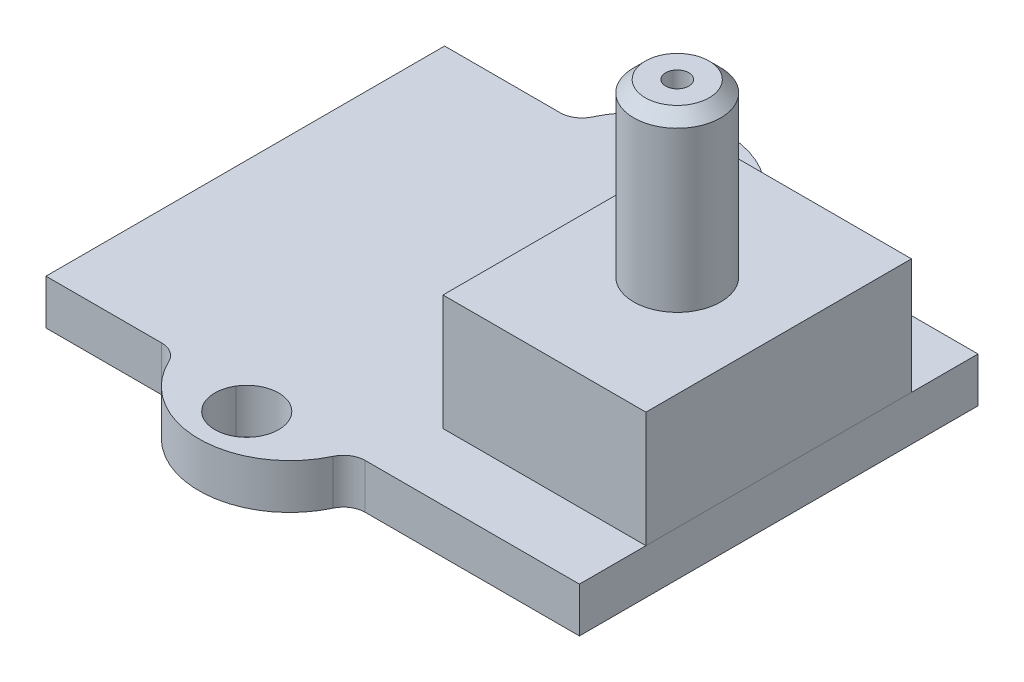
SolidWorks part; units mm, degrees
note: The reader was unsure of these and kept them because the rebuilt part matched: shared geometry of "Sketch1<3>", "Sketch1<4>".
ref_plane "Front Plane" through (0, 0, 0) normal (0, 0, 1) x (1, 0, 0)
ref_plane "Top Plane" through (0, 0, 0) normal (0, 1, 0) x (1, 0, 0)
ref_plane "Right Plane" through (0, 0, 0) normal (1, 0, 0) x (0, 0, -1)
sketch "Sketch1" plane through (0, 0, 0) normal (0, 1, 0) x (1, 0, 0)
  line L0 (-1.7, -9.1) -> (-1.7, 9.1) construction
  line L1 (-9.2, -6.875) -> (9.2, -6.875)
  line L2 (-9.2, -6.875) -> (-9.2, 6.875)
  line L3 (-9.2, 6.875) -> (9.2, 6.875)
  line L4 (9.2, -6.875) -> (9.2, 6.875)
  line L5 (-9.2, -6.875) -> (9.2, 6.875) construction
  line L6 (-9.2, 6.875) -> (9.2, -6.875) construction
  line L8 (2.2, -4.58) -> (9.2, -4.58)
  line L9 (2.2, -4.58) -> (2.2, 4.58)
  line L10 (2.2, 4.58) -> (9.2, 4.58)
  line L11 (9.2, -4.58) -> (9.2, 4.58)
  line L12 (2.2, -4.58) -> (9.2, 4.58) construction
  line L13 (2.2, 4.58) -> (9.2, -4.58) construction
  circle A0 centre (-1.7, 7.45) radius 1.1
  circle A1 centre (-1.7, -7.45) radius 1.1
  arc A2 (-4.7, 6.875) -> (1.3, 6.875) centre (-1.7, 5.965) cw
  arc A3 (-4.7, -6.875) -> (1.3, -6.875) centre (-1.7, -5.965) ccw
  circle A4 centre (5.7, 0) radius 1.5
  circle A5 centre (5.7, 0) radius 0.4
  point P0 (0, 0)
  point P13 (-1.7, -9.1)
  point P19 (-1.7, 0)
  point P20 (5.7, 0)
  point P21 (-1.7, 9.1)
  dimension "D3" = 2.2
  dimension "D8" = 18.2
  dimension "D11" = 3
  dimension "D12" = 0.8
  dimension "D1" = 18.4
  dimension "D2" = 13.75
  dimension "D4" = 7.5
  dimension "D5" = 14.9
  dimension "D6" = 7.45
  dimension "D7" = 6
  dimension "D9" = 7
  dimension "D10" = 9.16
extrude "Boss-Extrude1" add sketch "Sketch1" along normal blind 1.55 contours A1 L1 L4 L3 A0 L2 | L1 A1 | L1 A3 A1 | A2 L3 A0 | L10 L9 L8 L4 | A4 A5 | A5
extrude "Boss-Extrude2" add sketch "Sketch1<3>" along normal blind 3.99 from surface at 1.55 separate body contours L10 L9 L8 L4 A4 | A4 A5 | A5 starting at face at (-0.85, 1.55, 0)
sketch "Sketch1<3>" plane through (0, 0, 0) normal (0, 1, 0) x (1, 0, 0) same geometry as "Sketch1"
extrude "Boss-Extrude3" add sketch "Sketch1<4>" along normal blind 5.9 from surface at 5.54 contours A4 A5 starting at face at (5.7, 5.54, 0)
sketch "Sketch1<4>" plane through (0, 0, 0) normal (0, 1, 0) x (1, 0, 0) same geometry as "Sketch1"
chamfer "Chamfer1" distance 0.4 angle 45 1 edges at (5.7, 11.44, 1.5)
fillet "Fillet1" radius 0.75 4 edges at (-4.7, 0.775, -6.875) (1.3, 0.775, -6.875) (1.3, 0.775, 6.875) (-4.7, 0.775, 6.875)
